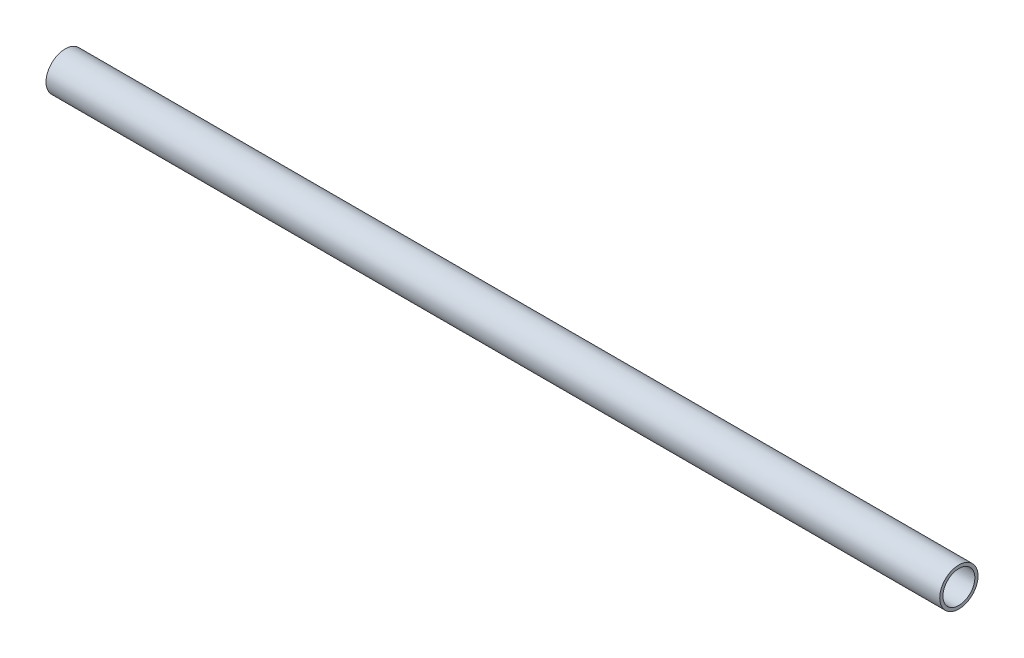
SolidWorks part; units mm, degrees
material "Brass"
ref_plane "Ebene vorne" through (0, 0, 0) normal (0, 0, 1) x (1, 0, 0)
ref_plane "Ebene oben" through (0, 0, 0) normal (0, 1, 0) x (1, 0, 0)
ref_plane "Ebene rechts" through (0, 0, 0) normal (1, 0, 0) x (0, 0, -1)
sketch "Sketch1" plane through (0, 0, 0) normal (0, 1, 0) x (1, 0, 0)
  line L0 (-0.9565, 0) -> (27.6627, 0) construction
  line L2 (0, 3) -> (140, 3)
  line L3 (0, 3) -> (0, 2.5)
  line L4 (0, 2.5) -> (140, 2.5)
  line L5 (140, 3) -> (140, 2.5)
  dimension "D1" = 6
  dimension "D2" = 5
  dimension "D3" = 140
revolve "Revolve1" add sketch "Sketch1" angle 360 about L0
